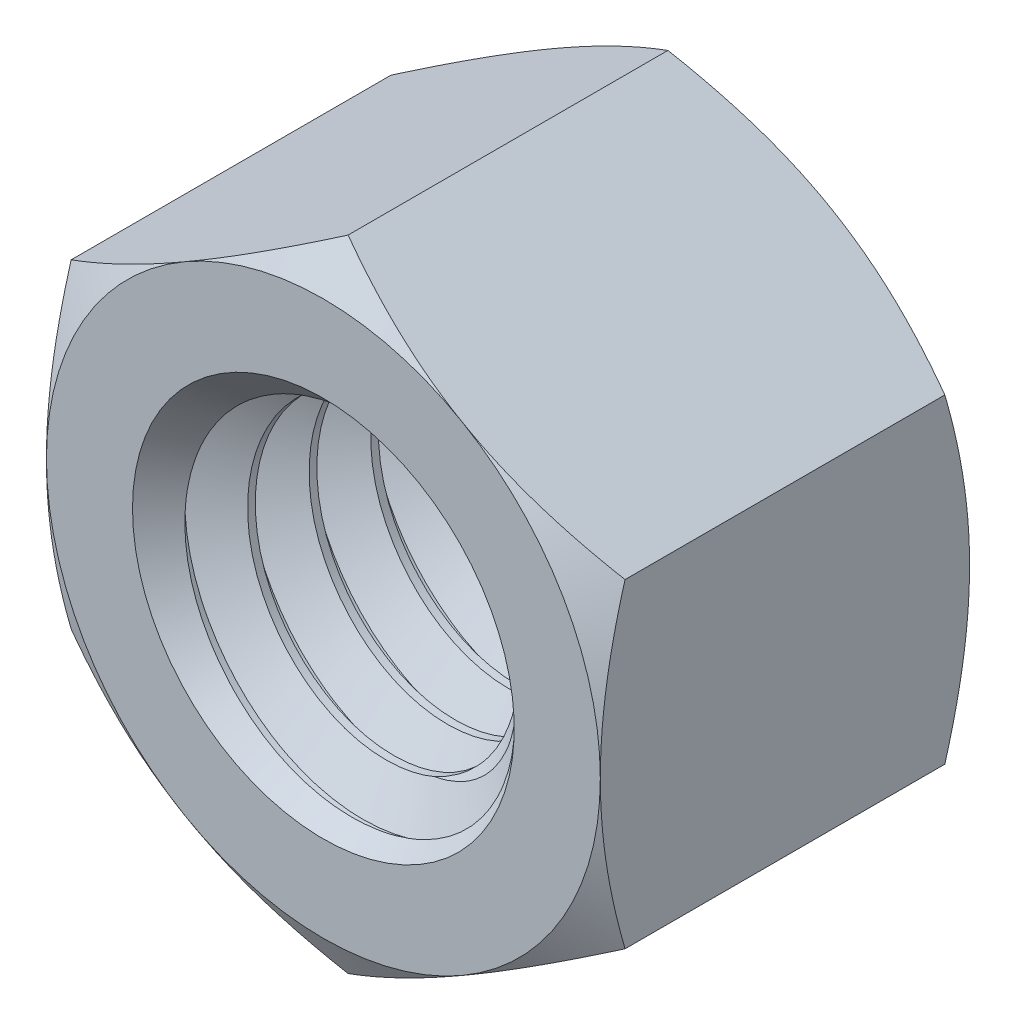
SolidWorks part; units mm, degrees
ref_plane "Front Plane" through (0, 0, 0) normal (0, 0, 1) x (1, 0, 0)
ref_plane "Top Plane" through (0, 0, 0) normal (0, 1, 0) x (1, 0, 0)
ref_plane "Right Plane" through (0, 0, 0) normal (1, 0, 0) x (0, 0, -1)
sketch "Sketch3" plane through (0, 0, 0) normal (1, 0, 0) x (0, 0, -1)
  line L0 (-1.5, 0) -> (1.5, 0) construction
  line L1 (0, 2.25) -> (0, -2.25) construction
  line L2 (-1.5, 1.5) -> (-1.5, -1.5) construction
  point P2 (-11.2, 0)
  point P3 (11.2, 0)
  dimension "Length" = 3
  dimension "Min Thread Length" = 12.7
  dimension "D1" = 12.7
  dimension "Thread Dia" = 3
  dimension "Hex" = 4.5
sketch "Sketch1" plane through (0, 0, 0) normal (0, 0, 1) x (1, 0, 0)
  line L1 (0, 2.5981) -> (-2.25, 1.299)
  line L2 (-2.25, 1.299) -> (-2.25, -1.299)
  line L3 (-2.25, -1.299) -> (0, -2.5981)
  line L4 (0, -2.5981) -> (2.25, -1.299)
  line L5 (2.25, -1.299) -> (2.25, 1.299)
  line L6 (2.25, 1.299) -> (0, 2.5981)
  circle A0 centre (0, 0) radius 2.25 construction
  circle A1 centre (0, 0) radius 1.5
extrude "Extrude1" add sketch "Sketch1" along normal up to vertex (1.5 mm away) and the other way up to vertex (1.5 mm away) up to point (0, 0, 1.5) other way up to point (0, 0, -1.5)
sketch "Sketch11" plane through (0, 0, -1.5) normal (0, 0, -1) x (-1, 0, 0)
  circle A0 centre (0, 0) radius 1.5 construction
  circle A1 centre (0, 0) radius 1.5
curve "Helix/Spiral1" pitch 0.5 height 3.5 radius 1.5 centre (0, 0, -1.5) axis (0, 0, 1) start towards (0, 1, 0) parameters "Pitch"=0.5
sketch "Sketch12" plane through (0, 0, 0) normal (1, 0, 0) x (0, 0, -1)
  line L0 (1.9375, 1.5) -> (1.5, 1.5)
  line L1 (1.9375, 1.5) -> (1.75, 1.1752)
  line L2 (1.75, 1.1752) -> (1.6875, 1.1752)
  line L3 (1.6875, 1.1752) -> (1.5, 1.5)
  line L4 (1.7187, 1.1752) -> (1.7187, 1.5) construction
  line L5 (1.8438, 1.3376) -> (1.5937, 1.3376) construction
  dimension "D1" = 0.0625
  dimension "D2" = 0.25
  dimension "D3" = 60
sweep "Sweep1" add profiles "Sketch12" path "Helix/Spiral1"
sketch "Sketch6" plane through (0, 0, -1.5) normal (0, 0, -1) x (-1, 0, 0)
  line L6 (0, 2.5981) -> (-2.25, 1.299)
  line L7 (-2.25, 1.299) -> (-2.25, -1.299)
  line L8 (-2.25, -1.299) -> (0, -2.5981)
  line L9 (0, -2.5981) -> (2.25, -1.299)
  line L10 (2.25, -1.299) -> (2.25, 1.299)
  line L11 (2.25, 1.299) -> (0, 2.5981)
  line L12 (0, 2.5981) -> (-2.25, 1.299)
  line L13 (-2.25, 1.299) -> (-2.25, -1.299)
  line L14 (-2.25, -1.299) -> (0, -2.5981)
  line L15 (0, -2.5981) -> (2.25, -1.299)
  line L16 (2.25, -1.299) -> (2.25, 1.299)
  line L17 (2.25, 1.299) -> (0, 2.5981)
  dimension "D1" = 0
extrude "Extrude2" cut sketch "Sketch6" along normal through all
sketch "Sketch7" plane through (0, 0, -1.5) normal (0, 0, -1) x (-1, 0, 0)
  circle A2 centre (0, 0) radius 1.5508
  circle A3 centre (0, 0) radius 1.5508
  dimension "D1" = 0.0508
extrude "Extrude3" cut sketch "Sketch7" against normal through all draft 43
sketch "Sketch8" plane through (0, 0, -1.5) normal (0, 0, -1) x (-1, 0, 0)
  circle A0 centre (0, 0) radius 2.25 construction
  circle A1 centre (0, 0) radius 2.25
extrude "Extrude4" cut sketch "Sketch8" against normal through all draft 60 flip side to cut
mirror "Mirror1" about plane through (0, 0, 0) normal (0, 0, 1) of "Extrude2", "Extrude3", "Extrude4"
sketch "Sketch9" [suppressed] plane through (0, 0, 0) normal (1, 0, 0) x (0, 0, -1)
  line L1 (-12.7, 2.4638) -> (12.7, 2.4638)
  line L2 (-12.7, 2.4638) -> (-12.7, 0)
  line L3 (-12.7, 0) -> (12.7, 0)
  line L4 (12.7, 2.4638) -> (12.7, 0)
  line L7 (-25.4, 0) -> (25.4, 0) construction
revolve "Revolve" [suppressed] add sketch "Sketch9" angle 360 about L0
sketch "Sketch10" [suppressed] plane through (0, 0, 0) normal (1, 0, 0) x (0, 0, -1)
  line L0 (25.4, 2.413) -> (12.7, 2.413)
  line L1 (-25.4, 2.413) -> (-12.7, 2.413)
  line L2 (12.7, 2.413) -> (12.7, -2.413)
  line L3 (-25.4, -2.4638) -> (-12.7, -2.4638)
  line L4 (-12.7, 2.413) -> (-12.7, -2.4638)
  line L5 (12.7, -2.413) -> (25.4, -2.413)
sketch "Sketch13" plane through (0, 0, 1.5) normal (0, 0, 1) x (1, 0, 0)
  line L0 (0.6959, 0.4402) -> (1.0897, 0.4402) construction
  line L1 (0.6959, 0.4402) -> (0.6959, -0.3853) construction
  line L2 (0.6959, 0.4402) -> (3.8103, 3.3481) construction
  arc A0 (0.5013, -1.063) -> (1.1082, -0.3912) centre (0, 0) ccw construction
  point P0 (0.6959, 0.4402)
  point P8 (-11.7542, 6.7404)
  point P9 (3.8103, 3.3481)
  point P10 (3.8103, 3.3481)
  point P11 (1.0897, 0.4402)
equation "\"D1@Sketch3\" = \"Min Thread Length@Sketch3\""
equation "\"D3@Helix/Spiral1\" = \"Length@Sketch3\"+\"Pitch@Helix/Spiral1\""
equation "\"D1@Sketch12\" = \"Pitch@Helix/Spiral1\"*.125"
equation "\"D2@Sketch12\" = \"Pitch@Helix/Spiral1\"*.5"
